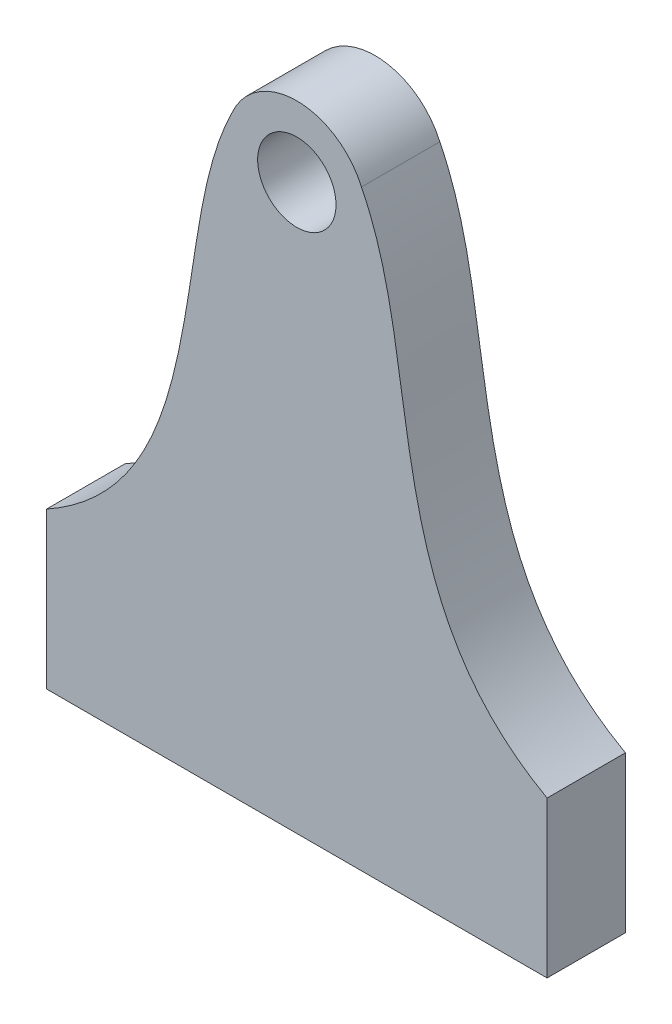
SolidWorks part; units mm, degrees
ref_plane "Front Plane" through (0, 0, 0) normal (0, 0, 1) x (1, 0, 0)
ref_plane "Top Plane" through (0, 0, 0) normal (0, 1, 0) x (1, 0, 0)
ref_plane "Right Plane" through (0, 0, 0) normal (1, 0, 0) x (0, 0, -1)
sketch "Sketch1" plane through (0, 0, 0) normal (0, 0, 1) x (1, 0, 0)
  line L0 (0, 0) -> (0, 45.72) construction
  line L1 (20.2849, 0) -> (20.2849, 12.6325)
  line L2 (20.2849, 0) -> (-20.2849, 0)
  line L5 (-20.2849, 0) -> (-20.2849, 12.6325)
  circle A0 centre (0, 45.72) radius 3.175
  arc A2 (5.2399, 48.0013) -> (-5.2399, 48.0013) centre (0, 45.72) ccw
  spline S0 degree 3 poles (-20.2849, 12.6325) (-11.3216, 17.627) (-9.1455, 30.7666) (-7.1272, 44.2326) (-5.2399, 48.0013) knots 0 0 0 0 0.567527 0.844926 0.844926 0.844926 0.844926
  spline S1 degree 3 poles (20.2849, 12.6325) (11.3216, 17.627) (9.1455, 30.7666) (7.1272, 44.2326) (5.2399, 48.0013) knots 0 0 0 0 0.567527 0.844926 0.844926 0.844926 0.844926
  dimension "D1" = 6.35
  dimension "D3" = 11.43
  dimension "D2" = 45.72
extrude "Boss-Extrude1" add sketch "Sketch1" along normal blind 6.35
